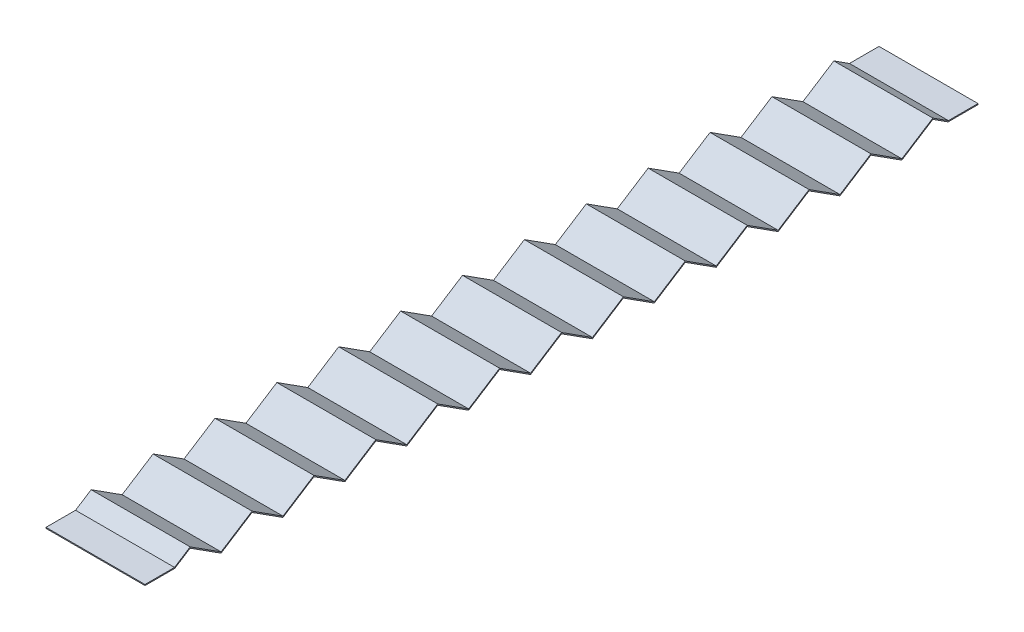
SolidWorks part; units mm, degrees
ref_plane "Front Plane" through (0, 0, 0) normal (0, 0, 1) x (1, 0, 0)
ref_plane "Top Plane" through (0, 0, 0) normal (0, 1, 0) x (1, 0, 0)
ref_plane "Right Plane" through (0, 0, 0) normal (1, 0, 0) x (0, 0, -1)
sketch "Sketch2" plane through (0, 0, 0) normal (0, 0, 1) x (1, 0, 0)
  line L1 (-27.5, 10) -> (27.5, 10)
  line L2 (-27.5, 10) -> (-27.5, 0)
  line L3 (-27.5, 0) -> (27.5, 0)
  line L4 (27.5, 10) -> (27.5, 0)
  point P4 (0, 0)
  dimension "D1" = 10
  dimension "D2" = 55
sketch "Sketch3" plane through (0, 0, 0) normal (1, 0, 0) x (0, 0, -1)
  line L0 (0, 10) -> (420.734, 10) construction
  line L1 (0, 0) -> (420.734, 0) construction
  line L3 (15, 5) -> (22.8147, 10)
  line L4 (22.8147, 10) -> (38.444, 0)
  line L5 (38.444, 0) -> (54.0734, 10)
  line L6 (54.0734, 10) -> (69.7028, 0)
  line L7 (69.7028, 0) -> (85.3321, 10)
  line L8 (85.3321, 10) -> (100.9615, 0)
  line L9 (100.9615, 0) -> (116.5909, 10)
  line L10 (116.5909, 10) -> (132.2202, 0)
  line L11 (132.2202, 0) -> (147.8496, 10)
  line L12 (147.8496, 10) -> (163.4789, 0)
  line L13 (163.4789, 0) -> (179.1083, 10)
  line L14 (179.1083, 10) -> (194.7377, 0)
  line L15 (194.7377, 0) -> (210.367, 10)
  line L16 (210.367, 10) -> (225.9964, 0)
  line L17 (225.9964, 0) -> (241.6257, 10)
  line L18 (241.6257, 10) -> (257.2551, 0)
  line L19 (0, 10) -> (0, 0) construction
  line L20 (257.2551, 0) -> (272.8845, 10)
  line L21 (272.8845, 10) -> (288.5138, 0)
  line L22 (288.5138, 0) -> (304.1432, 10)
  line L23 (304.1432, 10) -> (319.7726, 0)
  line L24 (319.7726, 0) -> (335.4019, 10)
  line L25 (335.4019, 10) -> (351.0313, 0)
  line L26 (351.0313, 0) -> (366.6606, 10)
  line L27 (366.6606, 10) -> (382.29, 0)
  line L28 (382.29, 0) -> (397.9194, 10)
  line L29 (397.9194, 10) -> (405.734, 5)
  line L30 (420.734, 10) -> (420.734, 0) construction
  line L31 (15, 5) -> (0, 5)
  line L32 (405.734, 5) -> (420.734, 5)
  line L33 (420.734, -12.75) -> (420.734, -19.8536) construction
  dimension "D2" = 15
  dimension "D1" = 10
  dimension "D3" = 15
extrude "Extrude-Thin1" add sketch "Sketch3" against normal mid plane 50 thin thin type mid plane wall 0.5
